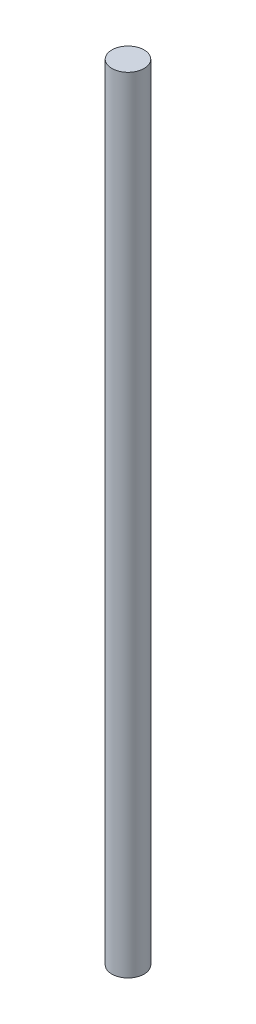
SolidWorks part; units mm, degrees
ref_plane "Płaszczyzna przednia" through (0, 0, 0) normal (0, 0, 1) x (1, 0, 0)
ref_plane "Płaszczyzna górna" through (0, 0, 0) normal (0, 1, 0) x (1, 0, 0)
ref_plane "Płaszczyzna prawa" through (0, 0, 0) normal (1, 0, 0) x (0, 0, -1)
sketch "Szkic1" plane through (0, 0, 0) normal (0, 1, 0) x (1, 0, 0)
  circle A0 centre (0, 0) radius 1.5
  dimension "D1" = 3
extrude "Dodanie-wyciągnięcie1" add sketch "Szkic1" along normal blind 73
